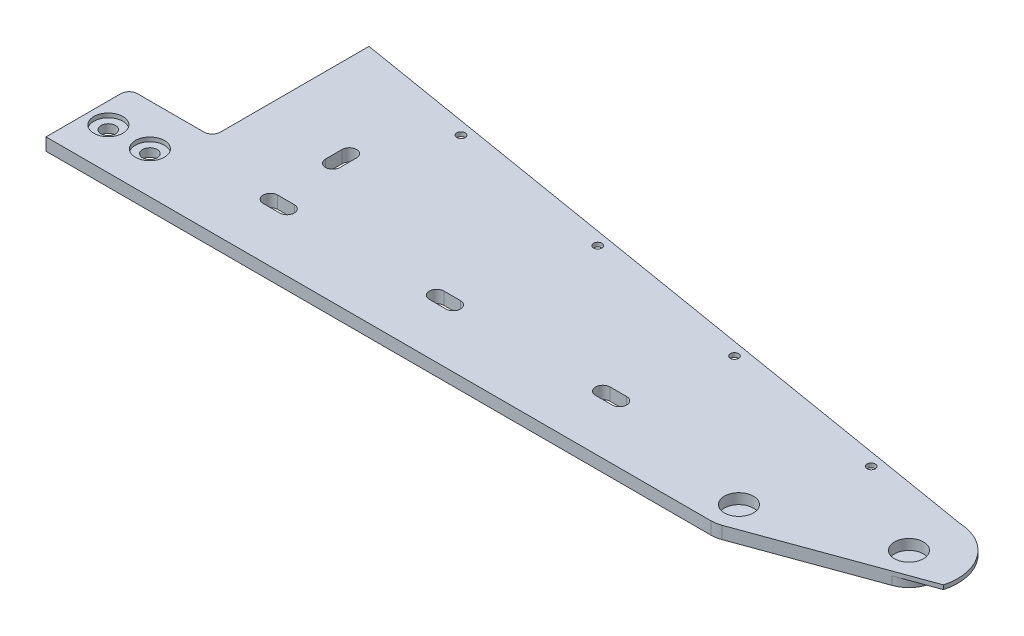
SolidWorks part; units mm, degrees
ref_plane "前视基准面" through (0, 0, 0) normal (0, 0, 1) x (1, 0, 0)
ref_plane "上视基准面" through (0, 0, 0) normal (0, 1, 0) x (1, 0, 0)
ref_plane "右视基准面" through (0, 0, 0) normal (1, 0, 0) x (0, 0, -1)
sketch "草图1" plane through (0, 0, 0) normal (0, 1, 0) x (1, 0, 0)
  line L1 (-17.5, -27.5) -> (17.5, -27.5)
  line L2 (-17.5, -27.5) -> (-17.5, 27.5)
  line L3 (-17.5, 27.5) -> (17.5, 27.5)
  line L4 (17.5, -27.5) -> (17.5, 27.5)
  line L5 (-17.5, -27.5) -> (17.5, 27.5) construction
  line L6 (-17.5, 27.5) -> (17.5, -27.5) construction
  point P0 (0, 0)
  dimension "D1" = 55
  dimension "D2" = 35
extrude "凸台-拉伸1" add sketch "草图1" along normal blind 1
sketch "草图2" plane through (0, 1, 0) normal (0, 1, 0) x (1, 0, 0)
  line L0 (-105.917, 0) -> (-62.25, 0) construction
  line L1 (106.75, 2.25) -> (121.75, 2.25)
  line L2 (-31.4474, 57.1013) -> (151.75, 26.6691)
  line L4 (124.0586, 2.6571) -> (154.0586, 13.5762)
  line L5 (-60.1618, 23.6059) -> (-42.6093, 52.0296)
  line L6 (121.75, 2.25) -> (121.75, 9) construction
  line L7 (121.75, -2.25) -> (121.75, -9) construction
  line L8 (-60.1618, -23.6059) -> (-42.6093, -52.0296)
  line L9 (124.0586, -2.6571) -> (154.0586, -13.5762)
  line L10 (121.75, -9) -> (128.5, -9)
  line L11 (-31.4474, -57.1013) -> (151.75, -26.6691)
  line L12 (106.75, -2.25) -> (121.75, -2.25)
  line L13 (-62.25, 16.25) -> (-62.25, -16.25)
  line L14 (106.75, 2.25) -> (106.75, -2.25)
  line L15 (106.75, 0) -> (124.0666, 0) construction
  arc A0 (-60.1618, 23.6059) -> (-62.25, 16.25) centre (-48.25, 16.25) ccw
  arc A1 (-31.4474, 57.1013) -> (-42.6093, 52.0296) centre (-33.25, 46.25) ccw
  arc A2 (121.75, 2.25) -> (124.0586, 2.6571) centre (121.75, 9) ccw
  arc A3 (154.0586, 13.5762) -> (151.75, 26.6691) centre (151.75, 19.9191) ccw
  arc A4 (154.0586, -13.5762) -> (151.75, -26.6691) centre (151.75, -19.9191) cw
  arc A5 (121.75, -2.25) -> (128.5, -9) centre (121.75, -9) cw
  arc A6 (-31.4474, -57.1013) -> (-42.6093, -52.0296) centre (-33.25, -46.25) cw
  arc A7 (-60.1618, -23.6059) -> (-62.25, -16.25) centre (-48.25, -16.25) cw
  line M10 (17.5, -27.5) -> (17.5, 27.5)
  line M11 (17.5, 27.5) -> (-17.5, 27.5)
  line M12 (-17.5, 27.5) -> (-17.5, -27.5)
  line M13 (-17.5, -27.5) -> (17.5, -27.5)
  dimension "D2" = 28
  dimension "D3" = 48.25
  dimension "D4" = 22
  dimension "D5" = 15
  dimension "D7" = 13.5
  dimension "D10" = 13.5
  dimension "D11" = 30
  dimension "D1" = 2.25
  dimension "D8" = 20
  dimension "D9" = 30
  dimension "D12" = 15
extrude "凸台-拉伸2" add sketch "草图2" along normal blind 3 contours A7 L8 A6 L11 A4 L9 A5 L12 L14 L1 A2 L4 A3 L2 A1 L5 A0 L13 | M13 M10 M11 M12 region at (37.3678, 1, 0) region at (0, 1, 0)
sketch "草图3" plane through (0, 4, 0) normal (0, 1, 0) x (1, 0, 0)
  circle A0 centre (-48.25, 16.25) radius 5
  circle A1 centre (-48.25, -16.25) radius 5
  circle A2 centre (-33.25, 46.25) radius 6.6982
  circle A3 centre (151.75, 19.9191) radius 2.5794
  circle A4 centre (121.75, 9) radius 2.5794
  circle A5 centre (121.75, -9) radius 2.5794
  circle A6 centre (151.75, -19.9191) radius 2.5794
  circle A7 centre (-33.25, -46.25) radius 6.6982
  dimension "D1" = 10
extrude "切除-拉伸1" cut sketch "草图3" against normal through all contours A0 | A1 region at (-48.25, 4, -16.25)
sketch "草图4" plane through (0, 4, 0) normal (0, 1, 0) x (1, 0, 0)
  circle A0 centre (-33.25, 46.25) radius 4
  circle A1 centre (-33.25, -46.25) radius 4
  dimension "D1" = 8
  dimension "D2" = 8
extrude "切除-拉伸2" cut sketch "草图4" against normal blind 2
sketch "草图5" plane through (0, 4, 0) normal (0, 1, 0) x (1, 0, 0)
  circle A0 centre (121.75, 9) radius 2
  circle A1 centre (121.75, -9) radius 2
  circle A2 centre (151.75, 19.9191) radius 2
  circle A3 centre (151.75, -19.9191) radius 2
  dimension "D1" = 4
extrude "切除-拉伸3" cut sketch "草图5" against normal blind 2
sketch "草图8" plane through (0, 1, 0) normal (0, -1, 0) x (1, 0, 0)
  line L1 (-39.75, -26.25) -> (-26.75, -26.25)
  line L2 (-39.75, -26.25) -> (-39.75, -66.25)
  line L3 (-39.75, -66.25) -> (-26.75, -66.25)
  line L4 (-26.75, -26.25) -> (-26.75, -66.25)
  line L5 (-39.75, -26.25) -> (-26.75, -66.25) construction
  line L6 (-39.75, -66.25) -> (-26.75, -26.25) construction
  line L16 (124.0586, 2.6571) -> (154.0586, 13.5762)
  line L17 (151.75, 26.6691) -> (-31.4474, 57.1013)
  line L18 (-42.6093, 52.0296) -> (-60.1618, 23.6059)
  line L19 (-62.25, 16.25) -> (-62.25, -16.25)
  line L20 (-60.1618, -23.6059) -> (-42.6093, -52.0296)
  line L21 (-31.4474, -57.1013) -> (151.75, -26.6691)
  line L22 (154.0586, -13.5762) -> (124.0586, -2.6571)
  line L23 (121.75, -2.25) -> (106.75, -2.25)
  line L24 (106.75, -2.25) -> (106.75, 2.25)
  line L25 (106.75, 2.25) -> (121.75, 2.25)
  line L26 (124.0586, 2.6571) -> (154.0586, 13.5762)
  line L27 (151.75, 26.6691) -> (-31.4474, 57.1013)
  line L28 (-42.6093, 52.0296) -> (-60.1618, 23.6059)
  line L31 (-31.4474, -57.1013) -> (151.75, -26.6691)
  line L32 (154.0586, -13.5762) -> (124.0586, -2.6571)
  line L33 (121.75, -2.25) -> (106.75, -2.25)
  line L34 (106.75, -2.25) -> (106.75, 2.25)
  line L35 (106.75, 2.25) -> (121.75, 2.25)
  arc A8 (154.0586, 13.5762) -> (151.75, 26.6691) centre (151.75, 19.9191) ccw
  arc A9 (-31.4474, 57.1013) -> (-42.6093, 52.0296) centre (-33.25, 46.25) ccw
  arc A10 (-60.1618, 23.6059) -> (-62.25, 16.25) centre (-48.25, 16.25) ccw
  arc A11 (-62.25, -16.25) -> (-60.1618, -23.6059) centre (-48.25, -16.25) ccw
  arc A12 (-42.6093, -52.0296) -> (-31.4474, -57.1013) centre (-33.25, -46.25) ccw
  arc A13 (151.75, -26.6691) -> (154.0586, -13.5762) centre (151.75, -19.9191) ccw
  arc A14 (124.0586, -2.6571) -> (121.75, -2.25) centre (121.75, -9) ccw
  arc A15 (121.75, 2.25) -> (124.0586, 2.6571) centre (121.75, 9) ccw
  arc A16 (154.0586, 13.5762) -> (151.75, 26.6691) centre (151.75, 19.9191) ccw
  arc A17 (-31.4474, 57.1013) -> (-42.6093, 52.0296) centre (-33.25, 46.25) ccw
  arc A18 (-60.1618, 23.6059) -> (-62.25, 16.25) centre (-48.25, 16.25) ccw
  arc A19 (-62.25, -16.25) -> (-60.1618, -23.6059) centre (-48.25, -16.25) ccw
  arc A20 (-42.6093, -52.0296) -> (-31.4474, -57.1013) centre (-33.25, -46.25) ccw
  arc A21 (151.75, -26.6691) -> (154.0586, -13.5762) centre (151.75, -19.9191) ccw
  arc A22 (124.0586, -2.6571) -> (121.75, -2.25) centre (121.75, -9) ccw
  arc A23 (121.75, 2.25) -> (124.0586, 2.6571) centre (121.75, 9) ccw
  point P0 (-33.25, -46.25)
  arc M32 (-42.6093, -52.0296) -> (-31.4474, -57.1013) centre (-33.25, -46.25) ccw
  line M33 (-31.4474, -57.1013) -> (151.75, -26.6691)
  dimension "D1" = 13
  dimension "D2" = 40
  dimension "D3" = 0
extrude "凸台-拉伸3" add sketch "草图8" along normal blind 7 contours L4 L1 L2 M32 M33 region at (-33.2258, 1, -41.4837)
mirror "镜向1" about plane through (0, 0, 0) normal (0, 0, 1) of "凸台-拉伸3"
sketch "草图9" plane through (0, -6, 0) normal (0, -1, 0) x (1, 0, 0)
  line L0 (-39.75, -26.25) -> (-26.75, -26.25) construction
  line L2 (-38.25, -53.75) -> (-38.25, -27.75)
  line L3 (-38.25, -27.75) -> (-28.25, -27.75)
  line L4 (-28.25, -53.75) -> (-28.25, -27.75)
  line L5 (-35.5448, -54.7408) -> (-28.25, -27.75) construction
  line L6 (-38.25, -27.75) -> (-31.223, -53.75) construction
  line L8 (-28.25, -53.75) -> (-38.25, -53.75)
  point P0 (-33.25, -46.25)
  dimension "D1" = 10
  dimension "D2" = 1.5
  dimension "D3" = 26
extrude "切除-拉伸4" cut sketch "草图9" against normal through all from offset 1.5 offset against normal yes
mirror "镜向2" about plane through (0, 0, 0) normal (0, 0, 1) of "切除-拉伸4"
sketch "草图10" plane through (0, 0, -53.75) normal (0, 0, 1) x (1, 0, 0)
  line L4 (-38.25, -4.5) -> (-28.25, -4.5)
  line L5 (-28.25, -4.5) -> (-28.25, 4)
  line L6 (-28.25, 4) -> (-38.25, 4)
  line L7 (-38.25, 4) -> (-38.25, -4.5)
  line L8 (-38.25, -4.5) -> (-28.25, -4.5)
  line L9 (-28.25, -4.5) -> (-28.25, 4)
  line L10 (-28.25, 4) -> (-38.25, 4)
  line L11 (-38.25, 4) -> (-38.25, -4.5)
  circle A0 centre (-33.25, -1.5) radius 1.5
  dimension "D2" = 3
  dimension "D3" = 3
  dimension "D1" = 0
extrude "切除-拉伸5" cut sketch "草图10" against normal through all contours A0 region at (-33.25, -1.5, -53.75)
mirror "镜向3" about plane through (0, 0, 0) normal (0, 0, 1) of "切除-拉伸5"
sketch "草图12" plane through (0, 4, 0) normal (0, 1, 0) x (1, 0, 0)
  line L3 (152.5362, 34.6481) -> (-30.1364, 64.9932)
  line L5 (-42.6093, 52.0296) -> (-60.1618, 23.6059) construction
  line L6 (124.0586, 2.6571) -> (154.0586, 13.5762) construction
  line L10 (154.0586, -13.5762) -> (124.0586, -2.6571)
  line L11 (121.75, -2.25) -> (106.75, -2.25)
  line L12 (106.75, -2.25) -> (106.75, 2.25)
  line L13 (106.75, 2.25) -> (121.75, 2.25)
  line L14 (124.0586, 2.6571) -> (154.0586, 13.5762)
  line L15 (151.75, 26.6691) -> (-31.4474, 57.1013)
  line L16 (-42.6093, 52.0296) -> (-60.1618, 23.6059)
  line L17 (-62.25, 16.25) -> (-62.25, -16.25)
  line L18 (-60.1618, -23.6059) -> (-42.6093, -52.0296)
  line L19 (-31.4474, -57.1013) -> (151.75, -26.6691)
  line L23 (-62.25, 2.25) -> (121.75, 2.25)
  line L24 (124.0586, 2.6571) -> (166.3826, 18.0617)
  line L26 (-34.4695, 65.2108) -> (-60.1618, 23.6059)
  line L27 (-62.25, 16.25) -> (-62.25, 2.25)
  line L30 (-49.416, 56.233) -> (-66.9685, 27.8093) construction
  line L31 (-70.25, 16.25) -> (-70.25, -5.75) construction
  line L32 (-70.25, -5.75) -> (121.75, -5.75) construction
  line L33 (126.7948, -4.8605) -> (156.7948, 6.0586) construction
  line L34 (151.75, 26.6691) -> (-31.4474, 57.1013) construction
  arc A1 (166.3826, 18.0617) -> (152.5362, 34.6481) centre (151.75, 19.9191) ccw
  arc A2 (-30.1364, 64.9932) -> (-34.4695, 65.2108) centre (-33.25, 46.25) ccw
  arc A4 (-30.1364, 64.9932) -> (-49.416, 56.233) centre (-33.25, 46.25) ccw construction
  arc A5 (156.7948, 6.0586) -> (152.5362, 34.6481) centre (151.75, 19.9191) ccw construction
  arc A8 (124.0586, -2.6571) -> (121.75, -2.25) centre (121.75, -9) ccw
  arc A9 (121.75, 2.25) -> (124.0586, 2.6571) centre (121.75, 9) ccw
  arc A10 (154.0586, 13.5762) -> (151.75, 26.6691) centre (151.75, 19.9191) ccw
  arc A11 (-31.4474, 57.1013) -> (-42.6093, 52.0296) centre (-33.25, 46.25) ccw
  arc A12 (-60.1618, 23.6059) -> (-62.25, 16.25) centre (-48.25, 16.25) ccw
  arc A13 (-62.25, -16.25) -> (-60.1618, -23.6059) centre (-48.25, -16.25) ccw
  arc A14 (-42.6093, -52.0296) -> (-31.4474, -57.1013) centre (-33.25, -46.25) ccw
  arc A15 (151.75, -26.6691) -> (154.0586, -13.5762) centre (151.75, -19.9191) ccw
  arc A17 (121.75, 2.25) -> (124.0586, 2.6571) centre (121.75, 9) ccw
  arc A20 (-60.1618, 23.6059) -> (-62.25, 16.25) centre (-48.25, 16.25) ccw
  arc A24 (-66.9685, 27.8093) -> (-70.25, 16.25) centre (-48.25, 16.25) ccw construction
  arc A25 (121.75, -5.75) -> (126.7948, -4.8605) centre (121.75, 9) ccw construction
  arc A26 (-31.4474, 57.1013) -> (-42.6093, 52.0296) centre (-33.25, 46.25) ccw construction
  arc A27 (154.0586, 13.5762) -> (151.75, 26.6691) centre (151.75, 19.9191) ccw construction
  dimension "D1" = 0
  dimension "D2" = 8
extrude "凸台-拉伸4" add sketch "草图12" along normal blind 3
sketch "草图13" plane through (0, 4, 0) normal (0, -1, 0) x (1, 0, 0)
  line L1 (-119.1699, 86.8947) -> (214.8426, 86.8947)
  line L2 (-119.1699, 86.8947) -> (-119.1699, -74.5615)
  line L3 (-119.1699, -74.5615) -> (214.8426, -74.5615)
  line L4 (214.8426, 86.8947) -> (214.8426, -74.5615)
  line L5 (-119.1699, 86.8947) -> (214.8426, -74.5615) construction
  line L6 (-119.1699, -74.5615) -> (214.8426, 86.8947) construction
  point P0 (47.8363, 6.1666)
extrude "切除-拉伸6" cut sketch "草图13" along normal blind 10
sketch "草图14" plane through (0, 4, 0) normal (0, -1, 0) x (1, 0, 0)
  circle A0 centre (151.75, -19.9191) radius 3.5
  circle A1 centre (121.75, -9) radius 3.5
  dimension "D2" = 7
  dimension "D3" = 7
extrude "切除-拉伸7" cut sketch "草图14" against normal through all from offset 0.5 offset against normal yes
sketch "草图15" plane through (0, 4, 0) normal (0, -1, 0) x (1, 0, 0)
  circle A0 centre (-48.25, -16.25) radius 5
  dimension "D1" = 10
extrude "切除-拉伸8" cut sketch "草图15" against normal through all
sketch "草图17" plane through (0, 4, 0) normal (0, -1, 0) x (1, 0, 0)
  line L0 (-30.6281, -62.0337) -> (152.2188, -31.6598)
  line L1 (-34.4695, -65.2108) -> (-36.5044, -61.9155)
  line L3 (166.3826, -18.0617) -> (163.0963, -16.8656)
  line L5 (166.3826, -18.0617) -> (124.0586, -2.6571)
  line L6 (121.75, -2.25) -> (-62.25, -2.25)
  line L7 (-62.25, -2.25) -> (-62.25, -16.25)
  line L8 (-60.1618, -23.6059) -> (-34.4695, -65.2108)
  line L9 (-30.1364, -64.9932) -> (152.5362, -34.6481)
  line L14 (-30.1364, -64.9932) -> (152.5362, -34.6481)
  arc A0 (-36.5044, -61.9155) -> (-30.6281, -62.0337) centre (-33.25, -46.25) ccw
  arc A1 (152.2188, -31.6598) -> (163.0963, -16.8656) centre (151.75, -19.9191) ccw
  arc A2 (-34.2769, -62.217) -> (-30.6281, -62.0337) centre (-33.25, -46.25) ccw construction
  arc A3 (152.2188, -31.6598) -> (163.4065, -18.4395) centre (151.75, -19.9191) ccw construction
  arc A4 (124.0586, -2.6571) -> (121.75, -2.25) centre (121.75, -9) ccw
  arc A5 (-62.25, -16.25) -> (-60.1618, -23.6059) centre (-48.25, -16.25) ccw
  arc A6 (-34.4695, -65.2108) -> (-30.1364, -64.9932) centre (-33.25, -46.25) ccw
  arc A7 (152.5362, -34.6481) -> (166.3826, -18.0617) centre (151.75, -19.9191) ccw
  arc A10 (-34.4695, -65.2108) -> (-30.1364, -64.9932) centre (-33.25, -46.25) ccw
  arc A11 (152.5362, -34.6481) -> (166.3826, -18.0617) centre (151.75, -19.9191) ccw
  dimension "D1" = 0
  dimension "D2" = 3
extrude "凸台-拉伸5" add sketch "草图17" against normal blind 16 from surface starting at face at (-48.25, 7, -21.25)
sketch "草图23" plane through (0, 4, 0) normal (0, -1, 0) x (1, 0, 0)
  line L2 (-39.75, -56.6598) -> (-39.75, -26.25)
  line L3 (-39.75, -26.25) -> (-26.75, -26.25)
  line L4 (-26.75, -64.4306) -> (-26.75, -26.25)
  line L5 (166.3826, -18.0617) -> (124.0586, -2.6571)
  line L6 (121.75, -2.25) -> (-62.25, -2.25)
  line L7 (-62.25, -2.25) -> (-62.25, -16.25)
  line L8 (-60.1618, -23.6059) -> (-34.4695, -65.2108)
  line L9 (-30.1364, -64.9932) -> (152.5362, -34.6481)
  line L13 (-39.75, -56.6598) -> (-34.4695, -65.2108)
  line L14 (-30.1364, -64.9932) -> (-26.75, -64.4306)
  line L15 (-37.7079, -59.9667) -> (-26.75, -26.25) construction
  line L16 (-39.75, -26.25) -> (-27.311, -64.5238) construction
  arc A4 (124.0586, -2.6571) -> (121.75, -2.25) centre (121.75, -9) ccw
  arc A5 (-62.25, -16.25) -> (-60.1618, -23.6059) centre (-48.25, -16.25) ccw
  arc A6 (-34.4695, -65.2108) -> (-30.1364, -64.9932) centre (-33.25, -46.25) ccw
  arc A7 (152.5362, -34.6481) -> (166.3826, -18.0617) centre (151.75, -19.9191) ccw
  arc A10 (-34.4695, -65.2108) -> (-30.1364, -64.9932) centre (-33.25, -46.25) ccw
  dimension "D3" = 13
  dimension "D1" = 0
extrude "凸台-拉伸7" add sketch "草图23" along normal blind 7
sketch "草图24" plane through (0, -3, 0) normal (0, -1, 0) x (1, 0, 0)
  line L0 (-38.25, -53.75) -> (-28.25, -53.75)
  line L2 (-38.25, -53.75) -> (-38.25, -27.75)
  line L3 (-38.25, -27.75) -> (-28.25, -27.75)
  line L4 (-28.25, -64.75) -> (-28.25, -64.6798)
  line L5 (-26.75, -64.4306) -> (-26.75, -26.25)
  line L6 (-26.75, -26.25) -> (-39.75, -26.25)
  line L7 (-39.75, -26.25) -> (-39.75, -56.6598)
  line L8 (-39.75, -56.6598) -> (-34.4695, -65.2108)
  line L9 (-30.1364, -64.9932) -> (-26.75, -64.4306)
  line L14 (-28.6727, -64.75) -> (-28.25, -64.6798)
  line L16 (-38.25, -27.75) -> (-31.223, -53.75) construction
  line L17 (-28.25, -53.75) -> (-28.25, -27.75)
  line L19 (-34.754, -64.75) -> (-34.4695, -65.2108)
  line L20 (-35.277, -53.75) -> (-28.25, -27.75) construction
  arc A1 (-34.4695, -65.2108) -> (-30.1364, -64.9932) centre (-33.25, -46.25) ccw
  dimension "D3" = 10
  dimension "D4" = 26
  dimension "D1" = 0
extrude "切除-拉伸11" cut sketch "草图24" against normal through all from offset 1.5 contours L0 L17 L3 L2 region at (-33.25, -3, -40.75) offset against normal yes
sketch "草图25" plane through (0, 0, -53.75) normal (0, 0, 1) x (1, 0, 0)
  line L4 (-28.25, 7) -> (-38.25, 7)
  line L5 (-38.25, 7) -> (-38.25, -1.5)
  line L6 (-38.25, -1.5) -> (-28.25, -1.5)
  line L7 (-28.25, -1.5) -> (-28.25, 7)
  line L8 (-28.25, 7) -> (-38.25, 7)
  line L9 (-38.25, 7) -> (-38.25, -1.5)
  line L10 (-38.25, -1.5) -> (-28.25, -1.5)
  line L11 (-28.25, -1.5) -> (-28.25, 7)
  circle A0 centre (-33.25, 1.5) radius 1.5
  dimension "D2" = 3
  dimension "D3" = 3
  dimension "D1" = 0
extrude "切除-拉伸12" cut sketch "草图25" against normal through all contours A0 region at (-33.25, 1.5, -53.75)
thread "螺纹线2" pitch 0.6 method cut profile "螺纹线轮廓2" start angle 0, offset 0, length 15, pitch 0.6, diameter 3
ref_plane "基准面2" through (-34.75, 1.5, -53.75) normal (0, -1, 0) x (-1, 0, 0)
sketch "螺纹线轮廓2" plane through (-34.75, 1.5, -53.75) normal (0, -1, 0) x (-1, 0, 0)
  line L0 (0, 0) -> (0, 0.6) construction
  line L1 (0, 0) -> (0.3248, 0.1875)
  line L2 (0.3248, 0.1875) -> (0.3248, 0.2625)
  line L3 (0.3248, 0.2625) -> (0, 0.45)
  line L4 (0.3248, 0.225) -> (0, 0.225) construction
  line L11 (0, 0) -> (0, 0.45)
  point P2 (0, 0)
  dimension "Pitch" = 0.6
  dimension "Profile_Angle" = 60
  dimension "Profile_Land" = 0.075
  dimension "Profile_Height" = 0.3248
sketch "草图26" plane through (0, -3, 0) normal (0, -1, 0) x (1, 0, 0)
  line L5 (-26.75, -64.4306) -> (-26.75, -26.25)
  line L6 (-26.75, -26.25) -> (-39.75, -26.25)
  line L7 (-39.75, -26.25) -> (-39.75, -56.6598)
  line L8 (-39.75, -56.6598) -> (-34.4695, -65.2108)
  line L9 (-30.1364, -64.9932) -> (-26.75, -64.4306)
  line L10 (-26.75, -64.4306) -> (-26.75, -26.25)
  line L11 (-26.75, -26.25) -> (-39.75, -26.25)
  line L12 (-39.75, -26.25) -> (-39.75, -56.6598)
  line L13 (-39.75, -56.6598) -> (-34.4695, -65.2108)
  line L14 (-30.1364, -64.9932) -> (-26.75, -64.4306)
  arc A1 (-34.4695, -65.2108) -> (-30.1364, -64.9932) centre (-33.25, -46.25) ccw
  arc A2 (-34.4695, -65.2108) -> (-30.1364, -64.9932) centre (-33.25, -46.25) ccw
  dimension "D1" = 0
extrude "切除-拉伸13" cut sketch "草图26" against normal through all
sketch "草图27" plane through (0, 4, 0) normal (0, -1, 0) x (1, 0, 0)
  line L0 (-45.75, -26.25) -> (-20.75, -26.25)
  line L1 (-20.75, -26.25) -> (-18.25, -26.25)
  line L2 (-18.25, -63.0186) -> (-18.25, -2.25)
  line L8 (-26.75, -26.25) -> (-26.75, -64.4306)
  line L9 (-26.75, -64.4306) -> (152.5362, -34.6481)
  line L10 (166.3826, -18.0617) -> (124.0586, -2.6571)
  line L11 (121.75, -2.25) -> (-62.25, -2.25)
  line L12 (-62.25, -2.25) -> (-62.25, -16.25)
  line L13 (-60.1618, -23.6059) -> (-39.75, -56.6598)
  line L14 (-39.75, -56.6598) -> (-39.75, -26.25)
  line L15 (-39.75, -26.25) -> (-26.75, -26.25)
  line L16 (-26.75, -26.25) -> (-26.75, -64.4306)
  line L17 (-26.75, -64.4306) -> (-18.25, -63.0186)
  line L19 (-18.25, -2.25) -> (-62.25, -2.25)
  line L20 (-62.25, -2.25) -> (-62.25, -16.25)
  line L21 (-60.1618, -23.6059) -> (-39.75, -56.6598)
  line L22 (-39.75, -56.6598) -> (-39.75, -26.25)
  line L23 (-39.75, -26.25) -> (-26.75, -26.25)
  circle A0 centre (-48.25, -16.25) radius 5 construction
  circle A1 centre (-48.25, -16.25) radius 5
  arc A3 (152.5362, -34.6481) -> (166.3826, -18.0617) centre (151.75, -19.9191) ccw
  arc A4 (124.0586, -2.6571) -> (121.75, -2.25) centre (121.75, -9) ccw
  arc A5 (-62.25, -16.25) -> (-60.1618, -23.6059) centre (-48.25, -16.25) ccw
  arc A8 (-62.25, -16.25) -> (-60.1618, -23.6059) centre (-48.25, -16.25) ccw
  point P12 (-33.25, -26.25)
  circle M14 centre (-48.25, -16.25) radius 5
  line M15 (-26.75, -26.25) -> (-26.75, -64.4306)
  line M16 (-26.75, -64.4306) -> (152.5362, -34.6481)
  line M20 (121.75, -2.25) -> (-62.25, -2.25)
  line M21 (-62.25, -2.25) -> (-62.25, -16.25)
  arc M22 (-62.25, -16.25) -> (-60.1618, -23.6059) centre (-48.25, -16.25) ccw
  line M23 (-60.1618, -23.6059) -> (-39.75, -56.6598)
  line M24 (-39.75, -56.6598) -> (-39.75, -26.25)
  line M25 (-39.75, -26.25) -> (-26.75, -26.25)
  dimension "D2" = 25
  dimension "D3" = 2.5
  dimension "D1" = 0
extrude "凸台-拉伸8" add sketch "草图27" along normal blind 2 contours L1 L2 L0 M20 M21 M22 M23 M24 M25 M14 | L2 L1 L0 M16 M15 region at (-40.852, 4, -19.0832) region at (-22.5267, 4, -44.9895)
sketch "草图28" plane through (0, 7, 0) normal (0, 1, 0) x (1, 0, 0)
  line L0 (-45.75, 26.25) -> (-20.75, 26.25)
  line L2 (-45.75, 26.25) -> (-45.75, 73.8905)
  line L3 (-20.75, 26.25) -> (-20.75, 73.8905)
  line L4 (-20.75, 73.8905) -> (-45.75, 73.8905)
  point P3 (-33.25, 26.25)
  dimension "D1" = 25
extrude "切除-拉伸14" cut sketch "草图28" along normal through all from offset 2 offset against normal yes
sketch "草图29" plane through (0, 7, 0) normal (0, 1, 0) x (1, 0, 0)
  circle A0 centre (-48.25, 16.25) radius 7.5
  dimension "D1" = 15
extrude "切除-拉伸15" cut sketch "草图29" against normal blind 4
sketch "草图31" plane through (0, 4, 0) normal (0, -1, 0) x (1, 0, 0)
  line L0 (-48.25, -16.25) -> (103.8912, -16.25)
  line L1 (1.75, -16.25) -> (5.75, -16.25) construction
  line L2 (1.75, -14.5) -> (5.75, -14.5)
  line L3 (1.75, -18) -> (5.75, -18)
  line L4 (41.75, -16.25) -> (45.75, -16.25) construction
  line L5 (41.75, -14.5) -> (45.75, -14.5)
  line L6 (41.75, -18) -> (45.75, -18)
  line L7 (81.75, -16.25) -> (85.75, -16.25) construction
  line L8 (81.75, -14.5) -> (85.75, -14.5)
  line L9 (81.75, -18) -> (85.75, -18)
  line L10 (1.75, -31.25) -> (1.75, -35.25) construction
  line L11 (3.5, -31.25) -> (3.5, -35.25)
  line L12 (0, -31.25) -> (0, -35.25)
  arc A0 (1.75, -14.5) -> (1.75, -18) centre (1.75, -16.25) ccw
  arc A1 (5.75, -18) -> (5.75, -14.5) centre (5.75, -16.25) ccw
  arc A2 (41.75, -14.5) -> (41.75, -18) centre (41.75, -16.25) ccw
  arc A3 (45.75, -18) -> (45.75, -14.5) centre (45.75, -16.25) ccw
  arc A4 (81.75, -14.5) -> (81.75, -18) centre (81.75, -16.25) ccw
  arc A5 (85.75, -18) -> (85.75, -14.5) centre (85.75, -16.25) ccw
  circle A6 centre (-48.25, -16.25) radius 5 construction
  arc A7 (3.5, -31.25) -> (0, -31.25) centre (1.75, -31.25) ccw
  arc A8 (0, -35.25) -> (3.5, -35.25) centre (1.75, -35.25) ccw
  point P5 (3.75, -16.25)
  point P10 (43.75, -16.25)
  point P17 (83.75, -16.25)
  point P28 (1.75, -33.25)
  dimension "D3" = 50
  dimension "D4" = 40
  dimension "D5" = 40
  dimension "D6" = 15
  dimension "D1" = 3.5
  dimension "D2" = 4
extrude "切除-拉伸16" cut sketch "草图31" against normal blind 10 contours L3 A1 L0 A0 | L0 A1 L2 A0 | L6 A3 L0 A2 | L0 A3 L5 A2 | L0 A5 L8 A4 | L9 A5 L0 A4 | L12 A8 L11 A7 region at (3.75, 4, -15.4289) region at (83.75, 4, -15.4289) region at (83.75, 4, -17.0711) region at (43.75, 4, -15.4289) region at (43.75, 4, -17.0711) region at (3.75, 4, -17.0711) region at (1.75, 4, -33.25)
sketch "草图32" plane through (0, 5, 0) normal (0, 1, 0) x (1, 0, 0)
  line L0 (-26.75, 26.25) -> (-20.75, 26.25)
  line L1 (-45.75, 26.25) -> (-39.75, 26.25)
  line L2 (-45.75, 26.25) -> (-20.75, 26.25) construction
  line L3 (-45.75, 26.25) -> (-39.75, 26.25) construction
  circle A0 centre (-42.75, 31.25) radius 1.8968
  circle A1 centre (-23.6075, 31.25) radius 1.8968
  circle A2 centre (-23.6075, 41.25) radius 1.8968
  circle A3 centre (-42.75, 41.25) radius 1.8968
  dimension "D2" = 10
  dimension "D3" = 5
  dimension "D4" = 10
  dimension "D1" = 5
extrude "切除-拉伸17" cut sketch "草图32" against normal blind 10 contours A3 | A0 | A2 | A1 region at (-42.75, 5, -31.25) region at (-23.6075, 5, -41.25) region at (-42.75, 5, -41.25)
sketch "草图33" plane through (0, 23, 0) normal (0, 1, 0) x (1, 0, 0)
  line L0 (-26.75, 56.321) -> (151.75, 26.6691)
  line L1 (124.0586, 2.6571) -> (163.0963, 16.8656) construction
  line L2 (154.0586, 13.5762) -> (163.0963, 16.8656)
  line L3 (-26.75, 64.4306) -> (-26.75, 26.25) construction
  line L4 (152.5362, 34.6481) -> (-20.75, 63.4339)
  line L5 (-20.75, 63.4339) -> (-20.75, 60.3928)
  line L6 (-20.75, 60.3928) -> (152.2188, 31.6598)
  line L7 (163.0963, 16.8656) -> (166.3826, 18.0617)
  line L8 (152.5362, 34.6481) -> (-20.75, 63.4339)
  line L11 (163.0963, 16.8656) -> (166.3826, 18.0617)
  line L12 (-26.75, 64.4306) -> (-26.75, 56.321)
  line L13 (-20.75, 63.4339) -> (-26.75, 64.4306) construction
  line L14 (-20.75, 63.4339) -> (-26.75, 64.4306)
  arc A0 (154.0586, 13.5762) -> (151.75, 26.6691) centre (151.75, 19.9191) ccw
  arc A2 (163.0963, 16.8656) -> (152.2188, 31.6598) centre (151.75, 19.9191) ccw
  arc A3 (166.3826, 18.0617) -> (152.5362, 34.6481) centre (151.75, 19.9191) ccw
  arc A5 (166.3826, 18.0617) -> (152.5362, 34.6481) centre (151.75, 19.9191) ccw
  dimension "D1" = 0
extrude "切除-拉伸18" cut sketch "草图33" along normal blind 2 from surface starting at face at (1.75, 4, -33.25)
sketch "草图34" plane through (0, 23, 0) normal (0, 1, 0) x (1, 0, 0)
  line L4 (152.5362, 34.6481) -> (-20.75, 63.4339)
  line L5 (-20.75, 63.4339) -> (-20.75, 60.3928)
  line L6 (-20.75, 60.3928) -> (152.2188, 31.6598)
  line L7 (163.0963, 16.8656) -> (166.3826, 18.0617)
  line L8 (152.5362, 34.6481) -> (-20.75, 63.4339)
  line L9 (-20.75, 63.4339) -> (-20.75, 60.3928)
  line L10 (-20.75, 60.3928) -> (152.2188, 31.6598)
  line L11 (163.0963, 16.8656) -> (166.3826, 18.0617)
  arc A2 (163.0963, 16.8656) -> (152.2188, 31.6598) centre (151.75, 19.9191) ccw
  arc A3 (166.3826, 18.0617) -> (152.5362, 34.6481) centre (151.75, 19.9191) ccw
  arc A4 (163.0963, 16.8656) -> (152.2188, 31.6598) centre (151.75, 19.9191) ccw
  arc A5 (166.3826, 18.0617) -> (152.5362, 34.6481) centre (151.75, 19.9191) ccw
  dimension "D1" = 0
extrude "切除-拉伸19" cut sketch "草图34" against normal through all
sketch "草图35" plane through (0, 6, 0) normal (0, -1, 0) x (1, 0, 0)
  line L0 (-20.75, -55.3243) -> (151.75, -26.6691) construction
  line L1 (-20.75, -55.3243) -> (151.75, -26.6691)
  line L2 (-20.75, -55.3243) -> (-34.502, -57.6087)
  line L3 (-34.502, -57.6087) -> (-32.1341, -71.8628)
  line L4 (-32.1341, -71.8628) -> (-8.5776, -67.9497)
  line L5 (-8.5776, -67.9497) -> (-10.9454, -53.6956)
  line M1 (-20.75, -60.3928) -> (152.2188, -31.6598)
  line M6 (-20.75, -55.3243) -> (-20.75, -60.3928)
extrude "切除-拉伸20" cut sketch "草图35" along normal through all contours L4 L5 L2 L3 M1 M6 | L5 L1 M1 M6 region at (-22.5812, 6, -63.7917) region at (-15.6401, 6, -57.0436)
sketch "草图36" plane through (0, 6, 0) normal (0, -1, 0) x (1, 0, 0)
  line L0 (-18.25, -54.909) -> (-18.25, -59.9775)
  line L1 (-20.75, -60.3928) -> (152.2188, -31.6598) construction
  line L2 (-18.25, -59.9775) -> (-20.75, -60.3928)
  line L3 (-20.75, -60.3928) -> (-20.75, -55.3243)
  line L4 (-20.75, -55.3243) -> (-18.25, -54.909)
extrude "切除-拉伸21" cut sketch "草图36" against normal through all
sketch "草图37" plane through (0, 6, 0) normal (0, -1, 0) x (1, 0, 0)
  line L1 (-18.25, -59.9775) -> (-18.25, -54.909) construction
  line L2 (-18.6597, -57.5113) -> (151.8091, -29.1935)
  line L3 (-18.25, -57.4432) -> (151.8091, -29.1935)
  line L4 (-18.25, -59.9775) -> (-18.25, -54.909)
  circle A0 centre (11.3445, -52.5271) radius 1
  circle A1 centre (50.8037, -45.9723) radius 1
  circle A2 centre (90.263, -39.4174) radius 1
  circle A3 centre (129.7223, -32.8625) radius 1
  dimension "D2" = 2
  dimension "D4" = 40
  dimension "D5" = 80
  dimension "D6" = 120
  dimension "D3" = 30
  dimension "D1" = 2.5
extrude "切除-拉伸22" cut sketch "草图37" against normal through all contours L3 A0 | L3 A0 | L3 A3 | L3 A3 | A1 | A2 region at (11.2749, 6, -52.1084) region at (129.6527, 6, -32.4439) region at (129.7918, 6, -33.2812) region at (11.414, 6, -52.9458)
sketch "草图39" plane through (0, 3, 0) normal (0, 1, 0) x (1, 0, 0)
  circle A0 centre (-48.25, 16.25) radius 5 construction
  circle A1 centre (-48.25, 16.25) radius 5
extrude "凸台-拉伸9" add sketch "草图39" against normal up to surface (1 mm away) up to face at (-42.75, 2, -33.1468)
sketch "草图40" plane through (-18.25, 0, 0) normal (-1, 0, 0) x (0, 0, 1)
  line L1 (-54.909, 7) -> (-57.3049, 7)
  line L2 (-54.909, 7) -> (-54.909, 1.313)
  line L3 (-54.909, 1.313) -> (-57.3049, 1.313)
  line L4 (-57.3049, 7) -> (-57.3049, 1.313)
extrude "切除-拉伸23" cut sketch "草图40" along normal through all
sketch "草图41" plane through (-18.25, 0, 0) normal (1, 0, 0) x (0, 0, -1)
  line L1 (-9.5041, 17.4332) -> (78.9894, 17.4332)
  line L2 (-9.5041, 17.4332) -> (-9.5041, -7.3959)
  line L3 (-9.5041, -7.3959) -> (78.9894, -7.3959)
  line L4 (78.9894, 17.4332) -> (78.9894, -7.3959)
extrude "切除-拉伸24" cut sketch "草图41" against normal through all
sketch "草图42" plane through (-18.25, 0, 0) normal (-1, 0, 0) x (0, 0, 1)
  line L0 (-59.9775, 7) -> (-2.25, 7) construction
  line L1 (-2.25, 4) -> (-22.25, 4)
  line L2 (-2.25, 4) -> (-2.25, 7)
  line L3 (-2.25, 7) -> (-22.25, 7)
  line L4 (-22.25, 4) -> (-22.25, 7)
  dimension "D1" = 20
extrude "凸台-拉伸10" add sketch "草图42" along normal blind 20
sketch "草图43" plane through (0, 4, 0) normal (0, -1, 0) x (1, 0, 0)
  line L0 (-38.25, -12.25) -> (-18.6294, -12.25) construction
  line L1 (-38.25, -22.25) -> (-38.25, -2.25) construction
  line L2 (-18.25, -54.909) -> (-18.25, -22.25) construction
  circle A0 centre (-33.25, -12.25) radius 1.75
  circle A1 centre (-23.25, -12.25) radius 1.75
  dimension "D1" = 3.5
  dimension "D2" = 3.5
  dimension "D4" = 10
  dimension "D3" = 5
extrude "切除-拉伸25" cut sketch "草图43" against normal blind 20
sketch "草图45" plane through (0, 7, 0) normal (0, 1, 0) x (1, 0, 0)
  circle A0 centre (-33.25, 12.25) radius 3.5
  circle A1 centre (-23.25, 12.25) radius 3.5
  dimension "D1" = 7
  dimension "D2" = 7
extrude "切除-拉伸26" cut sketch "草图45" against normal blind 1
fillet "圆角1" radius 2 2 edges at (-38.25, 5.5, -22.25) (-18.25, 5.5, -22.25)
